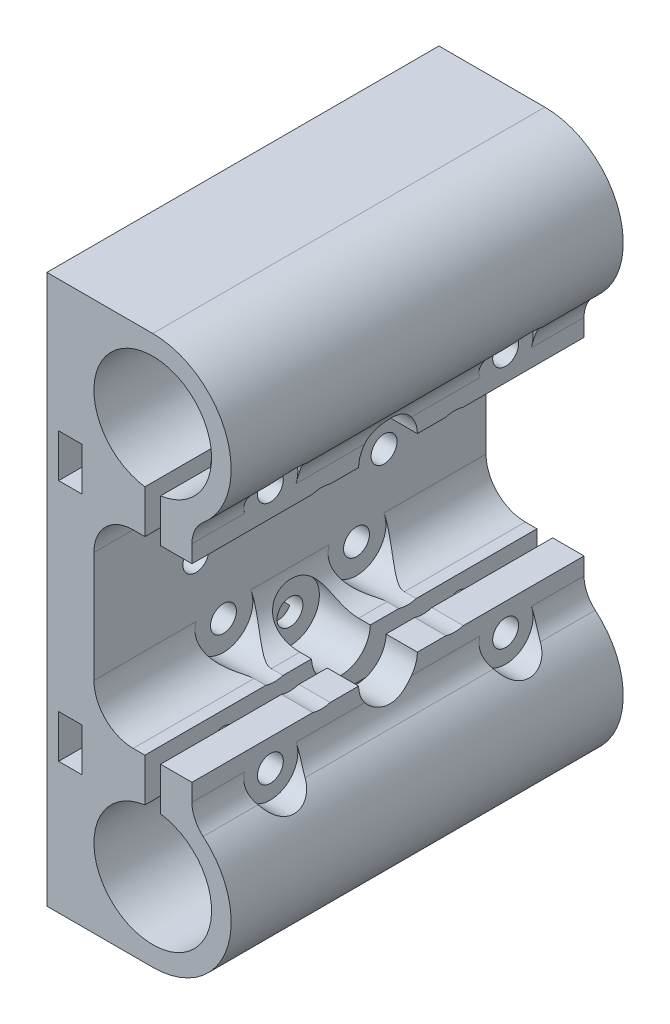
SolidWorks part; units mm, degrees
ref_plane "Plano frontal" through (0, 0, 0) normal (0, 0, 1) x (1, 0, 0)
ref_plane "Plano superior" through (0, 0, 0) normal (0, 1, 0) x (1, 0, 0)
ref_plane "Plano direito" through (0, 0, 0) normal (1, 0, 0) x (0, 0, -1)
sketch "Esboço1" plane through (0, 0, 0) normal (0, 0, 1) x (1, 0, 0)
  line L0 (0, 0) -> (67.7245, 0) construction
  line L1 (0, 35) -> (0, -35)
  line L2 (0, -35) -> (13.5, -35)
  line L3 (18.5, 14.2762) -> (18.5, 12.067)
  line L4 (18.5, 12.067) -> (14.5, 12.067)
  line L5 (12.5, -12.067) -> (11, -12.067)
  line L6 (6, -7.067) -> (6, 7.067)
  line L7 (12.5, -17.567) -> (12.5, -12.067)
  line L8 (14.5, 12.067) -> (14.5, 17.567)
  line L9 (12.5, 17.567) -> (12.5, 12.067)
  line L10 (13.5, 35) -> (0, 35)
  line L11 (12.5, 12.067) -> (11, 12.067)
  line L12 (14.5, -12.067) -> (14.5, -17.567)
  line L13 (18.5, -12.067) -> (14.5, -12.067)
  line L14 (18.5, -14.2762) -> (18.5, -12.067)
  line L15 (13.5, 25) -> (13.5, 21.6715) construction
  line L16 (4.5, -18.25) -> (1.5, -12.75) construction
  line L17 (4.5, 12.75) -> (1.5, 12.75)
  line L18 (4.5, 12.75) -> (4.5, 18.25)
  line L19 (4.5, 18.25) -> (1.5, 18.25)
  line L20 (1.5, 12.75) -> (1.5, 18.25)
  line L21 (4.5, 12.75) -> (1.5, 18.25) construction
  line L22 (4.5, 18.25) -> (1.5, 12.75) construction
  line L23 (4.5, -12.75) -> (1.5, -18.25) construction
  line L24 (1.5, -12.75) -> (1.5, -18.25)
  line L25 (4.5, -18.25) -> (1.5, -18.25)
  line L26 (4.5, -12.75) -> (4.5, -18.25)
  line L27 (4.5, -12.75) -> (1.5, -12.75)
  arc A0 (14.5, 17.567) -> (12.5, 17.567) centre (13.5, 25) ccw
  arc A1 (19.9286, -17.3401) -> (13.5, -35) centre (13.5, -25) cw
  arc A2 (19.9286, 17.3401) -> (13.5, 35) centre (13.5, 25) ccw
  arc A3 (14.5, -17.567) -> (12.5, -17.567) centre (13.5, -25) cw
  arc A4 (19.9286, -17.3401) -> (18.5, -14.2762) centre (22.5, -14.2762) cw
  arc A5 (18.5, 14.2762) -> (19.9286, 17.3401) centre (22.5, 14.2762) cw
  arc A6 (11, -12.067) -> (6, -7.067) centre (11, -7.067) cw
  arc A7 (11, 12.067) -> (6, 7.067) centre (11, 7.067) ccw
  point P1 (7.5394, 15.1781)
  point P3 (0, 0)
  point P28 (18.5, -16.3397)
  point P31 (18.5, 16.3397)
  point P32 (3, 15.5)
  point P37 (3.3733, 15.5)
  point P42 (3, -15.5)
  point P43 (0, 0)
  point P46 (6, -12.067)
  point P49 (6, 12.067)
  dimension "D1" = 15
  dimension "D2" = 5.5
  dimension "D5" = 10
  dimension "D8" = 4
  dimension "D13" = 5
  dimension "D3" = 6
  dimension "D4" = 70
  dimension "D6" = 2
  dimension "D7" = 4
  dimension "D9" = 9.5
  dimension "D10" = 5.5
  dimension "D11" = 3
  dimension "D12" = 3
extrude "Ressalto-extrusão1" add sketch "Esboço1" along normal blind 50
sketch "Esboço2" plane through (6, 0, 0) normal (1, 0, 0) x (0, 0, -1)
  line L1 (-25, 14.7551) -> (-25, -14.7551) construction
  line L3 (0, 0) -> (-50, 0) construction
  line L4 (-50, -7.067) -> (-50, 7.067) construction
  circle A0 centre (-25, 12) radius 1.65
  circle A1 centre (-16.5147, 8.4853) radius 1.65
  circle A2 centre (-13, 0) radius 1.65
  circle A3 centre (-16.5147, -8.4853) radius 1.65
  circle A4 centre (-25, -12) radius 1.65
  circle A5 centre (-33.4853, -8.4853) radius 1.65
  circle A6 centre (-37, 0) radius 1.65
  circle A7 centre (-33.4853, 8.4853) radius 1.65
  point P2 (-25.3127, 14.7551)
  point P3 (-25, 0)
  point P7 (-40.6698, 12.3727)
  point P29 (-40.6698, -12.3727)
  point P35 (-25, 0)
  point P53 (-25, 0)
  dimension "D4" = 3.3
  dimension "D5" = 12
  dimension "D6" = 8
extrude "Corte-extrusão1" cut sketch "Esboço2" against normal through all both and the other way through all
sketch "Esboço5" plane through (6, 0, 0) normal (1, 0, 0) x (0, 0, -1)
  line L0 (0, 0) -> (-50, 0) construction
  line L1 (-50, -7.067) -> (-50, 7.067) construction
  circle A0 centre (-25, 12) radius 3.75
  circle A1 centre (-16.5147, 8.4853) radius 3.75
  circle A2 centre (-13, 0) radius 3.75
  circle A3 centre (-16.5147, -8.4853) radius 3.75
  circle A4 centre (-25, -12) radius 3.75
  circle A5 centre (-33.4853, -8.4853) radius 3.75
  circle A6 centre (-37, 0) radius 3.75
  circle A7 centre (-33.4853, 8.4853) radius 3.75
  point P8 (-25, 0)
  point P25 (-25, 0)
  dimension "D1" = 7.5
  dimension "D2" = 8
extrude "Corte-extrusão2" cut sketch "Esboço5" along normal through all
sketch "Esboço6" plane through (14.5, 0, 0) normal (-1, 0, 0) x (0, 0, 1)
  line L1 (25, 35) -> (25, 0) construction
  line L2 (50, 35) -> (0, 35) construction
  line L3 (25, 0) -> (0, 0) construction
  line L4 (0, 32.5) -> (0, 17.567) construction
  line L6 (0, 25.0335) -> (50, 25.0335) construction
  line L7 (50, 17.567) -> (50, 32.5) construction
  circle A0 centre (10, 15.5335) radius 1.65
  circle A1 centre (40, 15.5335) radius 1.65
  circle A2 centre (40, -15.5335) radius 1.65
  circle A3 centre (10, -15.5335) radius 1.65
  point P20 (0, 0)
  dimension "D1" = 3.3
  dimension "D2" = 10
  dimension "D3" = 9.5
extrude "Corte-extrusão3" cut sketch "Esboço6" against normal through all both and the other way through all
sketch "Esboço7" plane through (18.5, 0, 0) normal (1, 0, 0) x (0, 0, -1)
  circle A0 centre (-40, 15.5335) radius 3.5
  circle A1 centre (-10, 15.5335) radius 3.5
  circle A2 centre (-10, -15.5335) radius 3.5
  circle A3 centre (-40, -15.5335) radius 3.5
  dimension "D1" = 7
extrude "Corte-extrusão4" cut sketch "Esboço7" along normal blind 10
sketch "Esboço4" plane through (6, 0, 0) normal (1, 0, 0) x (0, 0, -1)
  line L0 (0, -7.067) -> (0, 7.067) construction
  line L1 (0, -3.75) -> (-6.6629, -3.75)
  line L2 (0, -3.75) -> (0, -9.75)
  line L3 (0, -9.75) -> (-6.6629, -9.75)
  line L4 (-6.6629, -3.75) -> (-6.6629, -9.75)
  line L5 (0, 0) -> (-50, 0) construction
  line L6 (0, 3.75) -> (-6.6629, 3.75)
  line L7 (0, 3.75) -> (0, 9.75)
  line L8 (0, 9.75) -> (-6.6629, 9.75)
  line L9 (-6.6629, 3.75) -> (-6.6629, 9.75)
  line L10 (-50, -7.067) -> (-50, 7.067) construction
  dimension "D1" = 13.5
  dimension "D2" = 6
